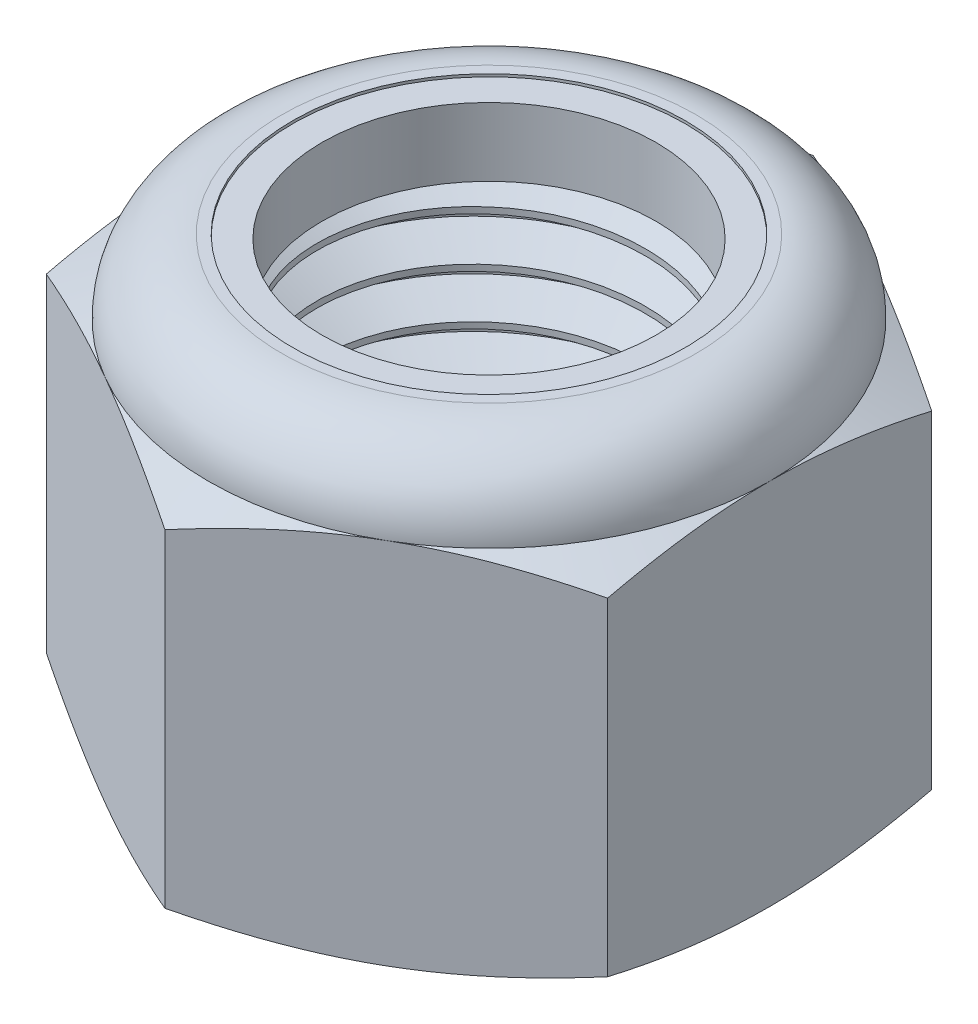
SolidWorks part; units mm, degrees
note: '?' marks a value the reader was unsure of.
ref_plane "Front" through (0, 0, 0) normal (0, 0, 1) x (1, 0, 0)
ref_plane "Top" through (0, 0, 0) normal (0, 1, 0) x (1, 0, 0)
ref_plane "Right" through (0, 0, 0) normal (1, 0, 0) x (0, 0, -1)
sketch "Sketch8" plane through (0, 0, 0) normal (1, 0, 0) x (0, 0, -1)
  line L0 (0, 0) -> (0, 25.0031) construction
  line L1 (15.875, 0) -> (-15.875, 0) construction
  line L2 (-11.1125, 25.0031) -> (11.1125, 25.0031) construction
  line L3 (11.1125, 25.0031) -> (11.1125, 22.1809) construction
sketch "Sketch1" plane through (0, 0, 0) normal (0, 1, 0) x (1, 0, 0)
  line L1 (0, 18.3309) -> (-15.875, 9.1654)
  line L2 (-15.875, 9.1654) -> (-15.875, -9.1654)
  line L3 (-15.875, -9.1654) -> (0, -18.3309)
  line L4 (0, -18.3309) -> (15.875, -9.1654)
  line L5 (15.875, -9.1654) -> (15.875, 9.1654)
  line L6 (15.875, 9.1654) -> (0, 18.3309)
  circle A0 centre (0, 0) radius 15.875 construction
  circle A1 centre (0, 0) radius 11.1125
extrude "Extrude1" add sketch "Sketch1" along normal up to vertex (25.0031 mm away) up to point (0, 25.0031, 0)
sketch "Sketch5" plane through (0, 0, 0) normal (1, 0, 0) x (0, 0, -1)
  line L0 (0, 0) -> (15.875, 0)
  line L1 (15.875, 0) -> (18.3309, 1.1452)
  line L2 (18.3309, 1.1452) -> (18.3309, 19.6907)
  line L3 (18.3309, 19.6907) -> (15.875, 20.8359)
  line L4 (11.7078, 25.0031) -> (11.7078, 26.2731)
  line L5 (11.7078, 26.2731) -> (19.6009, 26.2731)
  line L6 (19.6009, 26.2731) -> (19.6009, -1.27)
  line L7 (19.6009, -1.27) -> (0, -1.27)
  line L8 (0, -1.27) -> (0, 0)
  line L9 (15.875, 20.8359) -> (15.875, 0) construction
  line L12 (18.3309, 25.0031) -> (18.3309, 0) construction
  line L13 (18.3309, 12.5016) -> (19.6009, 12.5016) construction
  line L15 (0, 0) -> (0, 26.2731) construction
  line L18 (15.875, 0) -> (-15.875, 0) construction
  line L19 (9.1654, 25.0031) -> (18.3309, 25.0031) construction
  line L20 (0, 26.2731) -> (11.7078, 26.2731) construction
  line L21 (9.1654, 0) -> (18.3309, 0) construction
  arc A0 (15.875, 20.8359) -> (11.7078, 25.0031) centre (11.7078, 20.8359) ccw
  dimension "D1" = 25
  dimension "D2" = 1.27
  dimension "D4" = 4.1672
revolve "Cut-Revolve3" cut sketch "Sketch5" angle 360 about L15
sketch "Sketch4" plane through (0, 0, 0) normal (1, 0, 0) x (0, 0, -1)
  line L0 (0, 20.8359) -> (12.2237, 20.8359)
  line L1 (12.2237, 20.8359) -> (0, 15.1359)
  line L3 (0, 5.7) -> (12.2237, 0)
  line L4 (12.2237, 0) -> (0, 0)
  line L5 (0, 0) -> (0, 20.8359) construction
  line L10 (0, 0) -> (0, 25.0031) construction
  line L11 (0, 5.7) -> (0, 0)
  line L12 (0, 20.8359) -> (0, 15.1359)
  line L13 (13.7482, 20.8359) -> (0, 20.8359) construction
  dimension "D1" = 25
  dimension "D2" = 24.4475
sketch "Sketch6" plane through (0, 0, 0) normal (1, 0, 0) x (0, 0, -1)
  line L0 (0, 20.8359) -> (15.7226, 20.8359)
  line L1 (11.7078, 24.8507) -> (5.8539, 24.8507)
  line L2 (0, 26.2731) -> (0, 20.8359)
  line L3 (5.8539, 26.2731) -> (0, 26.2731)
  line L4 (0, 26.2731) -> (11.7078, 26.2731) construction
  line L5 (0, 0) -> (0, 26.2731) construction
  line L6 (0, 26.2731) -> (0, 0) construction
  line L7 (5.8539, 24.8507) -> (5.8539, 26.2731)
  line L8 (11.7078, 25.0031) -> (11.7078, 24.8507) construction
  line L9 (5.8539, 24.8507) -> (0, 24.8507) construction
  line L10 (0, 24.8507) -> (0, 15.1359) construction
  arc A0 (15.7226, 20.8359) -> (11.7078, 24.8507) centre (11.7078, 20.8359) ccw
  arc A1 (15.875, 20.8359) -> (11.7078, 25.0031) centre (11.7078, 20.8359) ccw construction
  dimension "D1" = 0.1524
revolve "Cut-Revolve4" cut sketch "Sketch6" angle 360 about L6
revolve "Cut-Revolve2" cut sketch "Sketch4" angle 360 about L5
sketch "Sketch7" plane through (0, 0, 0) normal (1, 0, 0) x (0, 0, -1)
  line L0 (9.4456, 20.9121) -> (15.6457, 20.9121)
  line L1 (11.7078, 24.7745) -> (9.4456, 24.7745)
  line L2 (9.4456, 24.7745) -> (9.4456, 20.9121)
  line L3 (9.4456, 20.9121) -> (0, 20.9121) construction
  line L4 (0, 20.9121) -> (0, 24.7745) construction
  line L5 (0, 24.7745) -> (9.4456, 24.7745) construction
  line L6 (9.4456, 20.9121) -> (9.4456, 20.8359) construction
  line L7 (0, 20.8359) -> (15.7226, 20.8359) construction
  line L8 (11.7078, 24.7745) -> (11.7078, 24.8507) construction
  arc A0 (15.6457, 20.9121) -> (11.7078, 24.7745) centre (11.7078, 20.8359) ccw
  arc A2 (15.7226, 20.8359) -> (11.7078, 24.8507) centre (11.7078, 20.8359) ccw construction
  dimension "D1" = 0.0762
  dimension "D2" = 18.8912
revolve "Revolve2" add sketch "Sketch7" angle 360 about L4
sketch "Sketch2" plane through (0, 0, 0) normal (1, 0, 0) x (0, 0, -1)
  line L0 (-11.1125, 0) -> (-11.1125, 20.8359) construction
  line L1 (0, 0) -> (11.1125, 0)
  line L2 (0, 0) -> (0, 20.8359)
  line L3 (0, 20.8359) -> (11.1125, 20.8359)
  line L4 (11.1125, 0) -> (11.1125, 20.8359)
  line L6 (13.7482, 20.8359) -> (15.875, 20.8359) construction
  line L7 (0, -11.1125) -> (0, 0) construction
revolve "Revolve1" add sketch "Sketch2" angle 360 about L7
sketch "Sketch9" plane through (0, 0, 0) normal (1, 0, 0) x (0, 0, -1)
  line L0 (11.418, 23.4818) -> (11.418, 20.6595) construction
  line L1 (11.418, 20.6595) -> (8.9739, 22.0707) construction
  line L2 (8.9739, 22.0707) -> (11.418, 23.4818) construction
  line L3 (9.2794, 22.247) -> (9.2794, 21.8943) construction
  line L4 (11.1125, 23.3054) -> (11.1125, 20.8359) construction
  line L5 (8.9739, 22.0707) -> (9.2794, 22.0707) construction
  line L6 (11.1125, 22.0707) -> (11.418, 22.0707) construction
  line L7 (11.2653, 22.0707) -> (11.2653, 23.3936) construction
  line L8 (11.418, 20.6595) -> (11.2653, 23.3936)
  line L9 (11.2653, 23.3936) -> (9.2794, 22.247)
  line L10 (9.2794, 22.247) -> (9.2794, 21.8943)
  line L11 (9.2794, 21.8943) -> (11.418, 20.6595)
  dimension "D1" = 2.8222
  dimension "D2" = 0.3528
sketch "Sketch10" plane through (0, 20.8359, 0) normal (0, 1, 0) x (1, 0, 0)
  circle A1 centre (0, 0) radius 11.1125
  circle A2 centre (0, 0) radius 11.1125
  dimension "D1" = 0
curve "Helix/Spiral1" pitch 2.8222 height 27.8253 turns 9.8594
sweep "Cut-Sweep1" cut profiles "Sketch9" path "Helix/Spiral1" align with end faces yes
sketch "Sketch11" plane through (0, 0, 0) normal (1, 0, 0) x (0, 0, -1)
  line L0 (0, 0) -> (0, 25.0031) construction
  line L1 (15.875, 0) -> (-15.875, 0) construction
  line L4 (0, 25.0031) -> (0, 0) construction
  line L5 (0, 12.5016) -> (11.1125, 12.5016) construction
  line L6 (0, 0) -> (12.2238, 0)
  line L7 (0, 5.7) -> (0, 0)
  line L8 (12.2238, 0) -> (0, 5.7)
  dimension "D1" = 24.4475
  dimension "D2" = 25
revolve "Revolve3" add sketch "Sketch11" angle 360 about L4
sketch "Sketch12" plane through (0, 0, 0) normal (1, 0, 0) x (0, 0, -1)
  line L0 (12.2237, 20.8359) -> (0, 20.8359)
  line L1 (0, 20.8359) -> (0, 0)
  line L2 (0, 0) -> (12.2237, 0)
  line L3 (15.875, 0) -> (-15.875, 0) construction
  line L4 (12.2237, 0) -> (12.2237, 20.8359)
  line L5 (-12.2237, 0) -> (12.2237, 0) construction
revolve "Revolve4" add sketch "Sketch12" angle 360 about L0
combine bodies "Combine1" operation type subtract main body 136 bodies to subtract 133
ref_plane "Contact Plane 1" through (0, 0, 0) normal (0, -1, 0) x (1, 0, 0)
ref_axis "Center Axis 1" through (0, -2.1015, 0) along (0, 1, 0)?
equation "\"D4@Sketch5\"=\"Height@Sketch8\"/6"
equation "\"D1@Sketch9\"=\"Thread Pitch@Sketch8\""
equation "\"D2@Sketch9\"=\"Thread Pitch@Sketch8\"/8"
equation "\"D4@Helix/Spiral1\"=\"Thread Pitch@Sketch8\""
equation "\"D3@Helix/Spiral1\"=\"Thread Pitch@Sketch8\"+\"Height@Sketch8\""
equation "\"D2@Sketch4\"=\"Thread Dia@Sketch8\"*1.1"
equation "\"D1@Sketch11\"=\"Thread Dia@Sketch8\"*1.1"
equation "\"D2@Sketch7\"=\"Thread Dia@Sketch8\"*.85"
